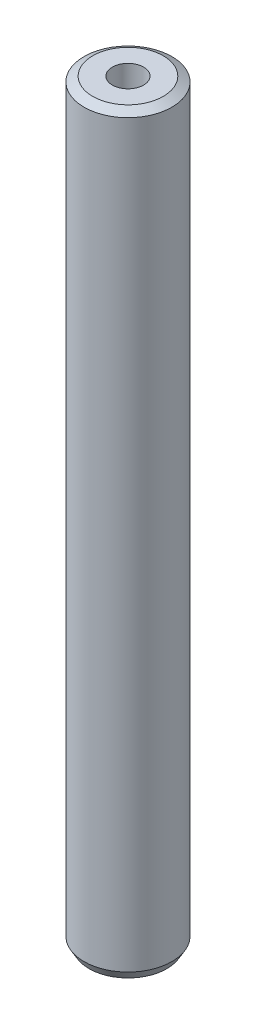
SolidWorks part; units mm, degrees
ref_plane "Front Plane" through (0, 0, 0) normal (0, 0, 1) x (1, 0, 0)
ref_plane "Top Plane" through (0, 0, 0) normal (0, 1, 0) x (1, 0, 0)
ref_plane "Right Plane" through (0, 0, 0) normal (1, 0, 0) x (0, 0, -1)
sketch "Sketch1" plane through (0, 0, 0) normal (0, 1, 0) x (1, 0, 0)
  circle A0 centre (0, 0) radius 5
  dimension "SHAFT_OD" = 10
extrude "Boss-Extrude1" add sketch "Sketch1" along normal blind 85.7919
sketch "Sketch2" plane through (0, 0, 0) normal (0, 1, 0) x (1, 0, 0)
  circle A0 centre (0, 0) radius 1.7791
  dimension "BORE_D" = 3.5581
extrude "Cut-Extrude1" cut sketch "Sketch2" along normal through all
chamfer "Chamfer1" distance 0.5695 angle 60 2 edges at (0, 85.7919, 5) (0, 0, 5) first distance on face at (0, 85.7919, 5) first distance on face at (0, 0, 1.7791)
